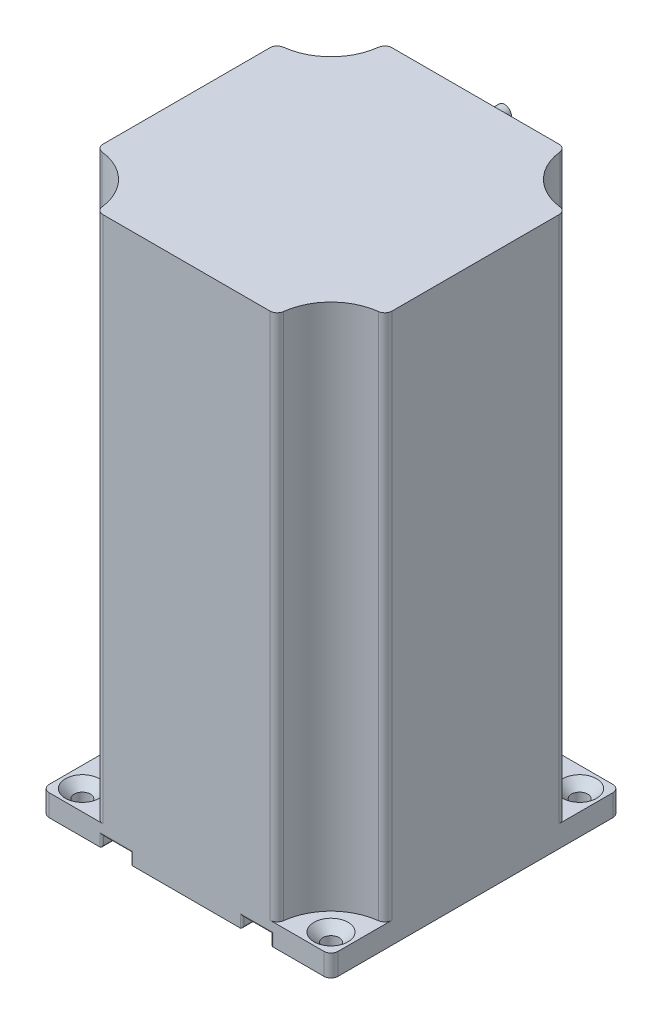
SolidWorks part; units mm, degrees
ref_plane "Płaszczyzna przednia" through (0, 0, 0) normal (0, 0, 1) x (1, 0, 0)
ref_plane "Płaszczyzna górna" through (0, 0, 0) normal (0, 1, 0) x (1, 0, 0)
ref_plane "Płaszczyzna prawa" through (0, 0, 0) normal (1, 0, 0) x (0, 0, -1)
sketch "Szkic1" plane through (0, 0, 0) normal (0, 1, 0) x (1, 0, 0)
  line L1 (40, -40) -> (-40, -40)
  line L2 (40, -40) -> (40, 40)
  line L3 (40, 40) -> (-40, 40)
  line L4 (-40, -40) -> (-40, 40)
  line L5 (40, -40) -> (-40, 40) construction
  line L6 (40, 40) -> (-40, -40) construction
  point P0 (0, 0)
  dimension "D1" = 80
  dimension "D2" = 80
extrude "Dodanie-wyciągnięcie1" add sketch "Szkic1" along normal blind 12
sketch "Szkic2" plane through (0, 12, 0) normal (0, 1, 0) x (1, 0, 0)
  circle A0 centre (-40, -40) radius 15
  dimension "D1" = 30
extrude "Wytnij-wyciągnięcie1" cut sketch "Szkic2" against normal blind 6
sketch "Szkic3" plane through (0, 12, 0) normal (0, 1, 0) x (1, 0, 0)
  line L0 (-52.6655, 0) -> (48.5858, 0) construction
  line L1 (0, 57.8416) -> (0, -51.7652) construction
mirror "Lustro1" about plane through (0, 0, 0) normal (1, 0, 0) of "Wytnij-wyciągnięcie1"
mirror "Lustro2" about plane through (0, 0, 0) normal (0, 0, 1) of "Lustro1"
fillet "Zaokrąglenie1" radius 2 12 edges at (-40, 3, -40) (-40, 9, -25) (-25, 9, -40) (40, 3, -40) (25, 9, -40) (40, 9, -25) (40, 3, 40) (40, 9, 25) (25, 9, 40) (-40, 9, 25) (-25, 9, 40) (-40, 3, 40)
hole_wizard "Pogłębienie stożkowe pod M4 Wkręt z łbem płaskim1" positions "Szkic6" profile "Szkic5" countersink size "M4" standard "ISO"
sketch "Szkic6" plane through (0, 6, 0) normal (0, 1, 0) x (1, 0, 0)
  line L4 (-39.4142, 39.4142) -> (-29.3934, 29.3934) construction
  arc A0 (-38, 40) -> (-40, 38) centre (-38, 38) ccw construction
  arc A1 (-38.2353, 25.1042) -> (-25.1042, 38.2353) centre (-40, 40) ccw construction
  point P0 (-34.4038, 34.4038)
  point P16 (-29.3934, 29.3934)
  point P20 (-34.0652, 34.0652)
  point P21 (-34.4038, 34.4038)
sketch "Szkic5" plane through (-34.4038, 6, -34.4038) normal (1, 0, 0) x (0, 0, 1)
  line L0 (0, 0) -> (0, 17.0319)
  line L1 (0, 17.0319) -> (2.25, 15.68)
  line L2 (2.25, 15.68) -> (2.25, 2.45)
  line L3 (2.25, 2.45) -> (4.7, 0)
  line L5 (4.7, 0) -> (0, 0)
  line L6 (-2.25, 2.45) -> (-4.7, 0) construction
  line L10 (0, 17.0319) -> (-2.25, 15.68) construction
  line L11 (0, -6.35) -> (0, 107.95) construction
  dimension "Średnica otworu" = 4.5
  dimension "Głębokośc otworu" = 15.68
  dimension "Średnica zewnętrznego pogłębienia stożkowego" = 9.4
  dimension "Kąt zewnętrznego pogłębienia stożkowego" = 90
  dimension "Kąt wiertła" = 118
mirror "Lustro3" about plane through (0, 0, 0) normal (0, 0, 1) of "Pogłębienie stożkowe pod M4 Wkręt z łbem płaskim1"
mirror "Lustro4" about plane through (0, 0, 0) normal (1, 0, 0) of "Lustro3"
sketch "Szkic8" plane through (0, 12, 0) normal (0, 1, 0) x (1, 0, 0)
  line L0 (-34.4038, 34.4038) -> (45.6548, 34.4038) construction
  line L2 (-6.6, 0) -> (6.6, 0) construction
  line L3 (0, -6.6) -> (0, 6.6) construction
  circle A0 centre (-19.4038, 34.4038) radius 2
  circle A1 centre (-19.4038, -34.4038) radius 2
  circle A2 centre (19.4038, 34.4038) radius 2
  circle A3 centre (19.4038, -34.4038) radius 2
  dimension "D1" = 4
  dimension "D2" = 15
extrude "Wytnij-wyciągnięcie2" cut sketch "Szkic8" against normal through all
sketch "Szkic9" plane through (0, 0, 0) normal (0, -1, 0) x (1, 0, 0)
  line L0 (15.4038, 34.4038) -> (15.4038, 40)
  line L1 (23.4038, 34.4038) -> (23.4038, 40)
  line L2 (23.4038, 40) -> (15.4038, 40)
  line L3 (-38, 40) -> (38, 40) construction
  line L4 (0, 51.7652) -> (0, -45.1724) construction
  line L5 (0, -57.8416) -> (0, 51.7652) construction
  line L6 (-54.6457, 0) -> (60.4895, 0) construction
  line L7 (-23.4038, 34.4038) -> (-23.4038, 40)
  line L8 (-15.4038, 34.4038) -> (-15.4038, 40)
  line L9 (-23.4038, 40) -> (-15.4038, 40)
  line L10 (23.4038, -34.4038) -> (23.4038, -40)
  line L11 (15.4038, -34.4038) -> (15.4038, -40)
  line L12 (23.4038, -40) -> (15.4038, -40)
  line L13 (-15.4038, -34.4038) -> (-15.4038, -40)
  line L14 (-23.4038, -40) -> (-15.4038, -40)
  line L15 (-23.4038, -34.4038) -> (-23.4038, -40)
  arc A0 (15.4038, 34.4038) -> (23.4038, 34.4038) centre (19.4038, 34.4038) ccw
  arc A1 (-15.4038, 34.4038) -> (-23.4038, 34.4038) centre (-19.4038, 34.4038) cw
  arc A2 (15.4038, -34.4038) -> (23.4038, -34.4038) centre (19.4038, -34.4038) cw
  arc A3 (-15.4038, -34.4038) -> (-23.4038, -34.4038) centre (-19.4038, -34.4038) ccw
  dimension "D1" = 4
extrude "Wytnij-wyciągnięcie3" cut sketch "Szkic9" against normal blind 3
fillet "Zaokrąglenie2" radius 0.5 24 edges at (15.4038, 0, 37.2019) (23.4038, 0, 37.2019) (-23.4038, 0, 37.2019) (-15.4038, 0, 37.2019) (23.4038, 0, -37.2019) (15.4038, 0, -37.2019) (-15.4038, 0, -37.2019) (-23.4038, 0, -37.2019) (19.4038, 3, 40) (19.4038, 0, 30.4038) (-19.4038, 3, 40) (-19.4038, 0, 30.4038) (19.4038, 0, -30.4038) (19.4038, 3, -40) (-19.4038, 3, -40) (-19.4038, 0, -30.4038) (-23.4038, 1.5, -40) (-15.4038, 1.5, -40) (15.4038, 1.5, -40) (23.4038, 1.5, -40) (-23.4038, 1.5, 40) (-15.4038, 1.5, 40) (15.4038, 1.5, 40) (23.4038, 1.5, 40)
sketch "Szkic10" plane through (0, 0, 0) normal (0, -1, 0) x (1, 0, 0)
  circle A0 centre (0, 0) radius 32.5
  dimension "D1" = 65
extrude "Dodanie-wyciągnięcie2" add sketch "Szkic10" along normal blind 0.5
fillet "Zaokrąglenie3" radius 0.5 1 edges at (0, -0.5, -32.5)
sketch "Szkic11" plane through (0, -0.5, 0) normal (0, -1, 0) x (1, 0, 0)
  circle A0 centre (0, 0) radius 7
  dimension "D1" = 14
extrude "Wytnij-wyciągnięcie4" cut sketch "Szkic11" against normal through all
chamfer "Sfazowanie1" distance 0.5 angle 45 1 edges at (0, -0.5, -7)
sketch "Szkic12" plane through (0, 12, 0) normal (0, 1, 0) x (1, 0, 0)
  line L4 (-40, 23.1181) -> (-40, -23.1181)
  line L5 (-23.1181, -40) -> (23.1181, -40)
  line L6 (40, -23.1181) -> (40, 23.1181)
  line L7 (23.1181, 40) -> (-23.1181, 40)
  line L8 (-40, 23.1181) -> (-40, -23.1181)
  line L9 (-23.1181, -40) -> (23.1181, -40)
  line L10 (40, -23.1181) -> (40, 23.1181)
  line L11 (23.1181, 40) -> (-23.1181, 40)
  circle A0 centre (0, 0) radius 7 construction
  circle A1 centre (-19.4038, -34.4038) radius 2 construction
  circle A2 centre (19.4038, -34.4038) radius 2 construction
  circle A3 centre (19.4038, 34.4038) radius 2 construction
  circle A4 centre (-19.4038, 34.4038) radius 2 construction
  circle A5 centre (0, 0) radius 7
  circle A6 centre (-19.4038, -34.4038) radius 2
  circle A7 centre (19.4038, -34.4038) radius 2
  circle A8 centre (19.4038, 34.4038) radius 2
  circle A9 centre (-19.4038, 34.4038) radius 2
  arc A12 (-38.2353, 25.1042) -> (-25.1042, 38.2353) centre (-40, 40) ccw
  arc A13 (-38.2353, 25.1042) -> (-40, 23.1181) centre (-38, 23.1181) ccw
  arc A14 (-40, -23.1181) -> (-38.2353, -25.1042) centre (-38, -23.1181) ccw
  arc A15 (-25.1042, -38.2353) -> (-38.2353, -25.1042) centre (-40, -40) ccw
  arc A16 (-25.1042, -38.2353) -> (-23.1181, -40) centre (-23.1181, -38) ccw
  arc A17 (23.1181, -40) -> (25.1042, -38.2353) centre (23.1181, -38) ccw
  arc A18 (38.2353, -25.1042) -> (25.1042, -38.2353) centre (40, -40) ccw
  arc A19 (38.2353, -25.1042) -> (40, -23.1181) centre (38, -23.1181) ccw
  arc A20 (40, 23.1181) -> (38.2353, 25.1042) centre (38, 23.1181) ccw
  arc A21 (25.1042, 38.2353) -> (38.2353, 25.1042) centre (40, 40) ccw
  arc A22 (25.1042, 38.2353) -> (23.1181, 40) centre (23.1181, 38) ccw
  arc A23 (-23.1181, 40) -> (-25.1042, 38.2353) centre (-23.1181, 38) ccw
  arc A24 (-38.2353, 25.1042) -> (-25.1042, 38.2353) centre (-40, 40) ccw
  arc A25 (-38.2353, 25.1042) -> (-40, 23.1181) centre (-38, 23.1181) ccw
  arc A26 (-40, -23.1181) -> (-38.2353, -25.1042) centre (-38, -23.1181) ccw
  arc A27 (-25.1042, -38.2353) -> (-38.2353, -25.1042) centre (-40, -40) ccw
  arc A28 (-25.1042, -38.2353) -> (-23.1181, -40) centre (-23.1181, -38) ccw
  arc A29 (23.1181, -40) -> (25.1042, -38.2353) centre (23.1181, -38) ccw
  arc A30 (38.2353, -25.1042) -> (25.1042, -38.2353) centre (40, -40) ccw
  arc A31 (38.2353, -25.1042) -> (40, -23.1181) centre (38, -23.1181) ccw
  arc A32 (40, 23.1181) -> (38.2353, 25.1042) centre (38, 23.1181) ccw
  arc A33 (25.1042, 38.2353) -> (38.2353, 25.1042) centre (40, 40) ccw
  arc A34 (25.1042, 38.2353) -> (23.1181, 40) centre (23.1181, 38) ccw
  arc A35 (-23.1181, 40) -> (-25.1042, 38.2353) centre (-23.1181, 38) ccw
  dimension "D1" = 0
extrude "Dodanie-wyciągnięcie3" add sketch "Szkic12" along normal blind 128
sketch "Szkic15" plane through (0, 140, 0) normal (0, 1, 0) x (1, 0, 0)
  line L4 (-40, 23.1181) -> (-40, -23.1181)
  line L5 (-23.1181, -40) -> (23.1181, -40)
  line L6 (40, -23.1181) -> (40, 23.1181)
  line L7 (23.1181, 40) -> (-23.1181, 40)
  line L8 (-40, 23.1181) -> (-40, -23.1181)
  line L9 (-23.1181, -40) -> (23.1181, -40)
  line L10 (40, -23.1181) -> (40, 23.1181)
  line L11 (23.1181, 40) -> (-23.1181, 40)
  arc A12 (-38.2353, 25.1042) -> (-40, 23.1181) centre (-38, 23.1181) ccw
  arc A13 (-40, -23.1181) -> (-38.2353, -25.1042) centre (-38, -23.1181) ccw
  arc A14 (-25.1042, -38.2353) -> (-38.2353, -25.1042) centre (-40, -40) ccw
  arc A15 (-25.1042, -38.2353) -> (-23.1181, -40) centre (-23.1181, -38) ccw
  arc A16 (23.1181, -40) -> (25.1042, -38.2353) centre (23.1181, -38) ccw
  arc A17 (38.2353, -25.1042) -> (25.1042, -38.2353) centre (40, -40) ccw
  arc A18 (38.2353, -25.1042) -> (40, -23.1181) centre (38, -23.1181) ccw
  arc A19 (40, 23.1181) -> (38.2353, 25.1042) centre (38, 23.1181) ccw
  arc A20 (25.1042, 38.2353) -> (38.2353, 25.1042) centre (40, 40) ccw
  arc A21 (25.1042, 38.2353) -> (23.1181, 40) centre (23.1181, 38) ccw
  arc A22 (-23.1181, 40) -> (-25.1042, 38.2353) centre (-23.1181, 38) ccw
  arc A23 (-38.2353, 25.1042) -> (-25.1042, 38.2353) centre (-40, 40) ccw
  arc A24 (-38.2353, 25.1042) -> (-40, 23.1181) centre (-38, 23.1181) ccw
  arc A25 (-40, -23.1181) -> (-38.2353, -25.1042) centre (-38, -23.1181) ccw
  arc A26 (-25.1042, -38.2353) -> (-38.2353, -25.1042) centre (-40, -40) ccw
  arc A27 (-25.1042, -38.2353) -> (-23.1181, -40) centre (-23.1181, -38) ccw
  arc A28 (23.1181, -40) -> (25.1042, -38.2353) centre (23.1181, -38) ccw
  arc A29 (38.2353, -25.1042) -> (25.1042, -38.2353) centre (40, -40) ccw
  arc A30 (38.2353, -25.1042) -> (40, -23.1181) centre (38, -23.1181) ccw
  arc A31 (40, 23.1181) -> (38.2353, 25.1042) centre (38, 23.1181) ccw
  arc A32 (25.1042, 38.2353) -> (38.2353, 25.1042) centre (40, 40) ccw
  arc A33 (25.1042, 38.2353) -> (23.1181, 40) centre (23.1181, 38) ccw
  arc A34 (-23.1181, 40) -> (-25.1042, 38.2353) centre (-23.1181, 38) ccw
  arc A35 (-38.2353, 25.1042) -> (-25.1042, 38.2353) centre (-40, 40) ccw
  dimension "D1" = 0
extrude "Dodanie-wyciągnięcie4" add sketch "Szkic15" along normal blind 12
sketch "Szkic16" plane through (0, 0, -40) normal (0, 0, -1) x (-1, 0, 0)
  line L0 (-23.1181, 152) -> (23.1181, 152) construction
  line L1 (-6, 148) -> (6, 148)
  line L2 (-6, 148) -> (-6, 140)
  line L3 (-6, 140) -> (6, 140)
  line L4 (6, 148) -> (6, 140)
  line L5 (-6, 148) -> (6, 140) construction
  line L6 (-6, 140) -> (6, 148) construction
  point P0 (0, 144)
  point P8 (0, 152)
  dimension "D1" = 8
  dimension "D2" = 12
  dimension "D3" = 8
extrude "Dodanie-wyciągnięcie5" add sketch "Szkic16" along normal blind 3
sketch "Szkic17" plane through (0, 0, -43) normal (0, 0, -1) x (-1, 0, 0)
  line L0 (6, 148) -> (-6, 148) construction
  line L1 (6, 140) -> (6, 148) construction
  circle A0 centre (0, 144) radius 2
  point P5 (0, 148)
  point P8 (6, 144)
  dimension "D1" = 4
extrude "Dodanie-wyciągnięcie6" add sketch "Szkic17" along normal blind 5
